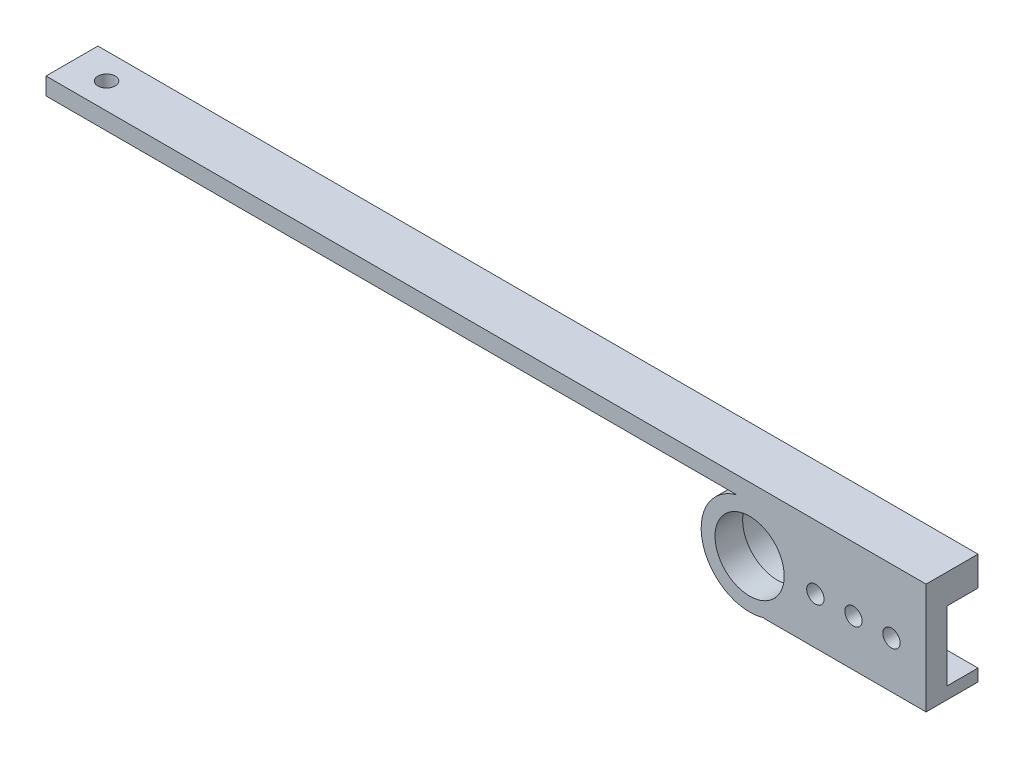
SolidWorks part; units mm, degrees
ref_plane "前视基准面" through (0, 0, 0) normal (0, 0, 1) x (1, 0, 0)
ref_plane "上视基准面" through (0, 0, 0) normal (0, 1, 0) x (1, 0, 0)
ref_plane "右视基准面" through (0, 0, 0) normal (1, 0, 0) x (0, 0, -1)
sketch "草图1" plane through (0, 0, 0) normal (0, 0, 1) x (1, 0, 0)
  line L1 (20, -10) -> (-20, -10)
  line L2 (20, -10) -> (20, 10)
  line L3 (20, 10) -> (-20, 10)
  line L4 (-20, -10) -> (-20, 10)
  line L5 (20, -10) -> (-20, 10) construction
  line L6 (20, 10) -> (-20, -10) construction
  point P0 (0, 0)
  dimension "D1" = 40
  dimension "D2" = 20
extrude "凸台-拉伸1" add sketch "草图1" along normal blind 6
sketch "草图2" plane through (0, 0, 6) normal (0, 0, 1) x (1, 0, 0)
  line L0 (20, -10) -> (20, 10) construction
  circle A0 centre (10, 0) radius 2.5
  circle A1 centre (-1, 0) radius 2.5
  circle A2 centre (-12, 0) radius 2.5
  dimension "D1" = 10
  dimension "D2" = 5
  dimension "D3" = 3
extrude "切除-拉伸1" cut sketch "草图2" against normal through all
sketch "草图3" plane through (0, 0, 6) normal (0, 0, 1) x (1, 0, 0)
  line L0 (20, 13.5) -> (20, 10)
  line L1 (20, -13.5) -> (-26.894, -13.5)
  line L3 (20, 13.5) -> (-26.894, 13.5)
  line L4 (-20, 10) -> (-20, -10)
  line L5 (-20, -10) -> (20, -10)
  line L6 (20, -10) -> (20, 10)
  line L7 (20, 10) -> (-20, 10)
  line L8 (-20, 10) -> (-20, -10)
  line L9 (-20, -10) -> (20, -10)
  line L10 (20, -10) -> (20, 10)
  line L11 (20, 10) -> (-20, 10)
  line L12 (-26.894, -13.5) -> (-26.894, 13.5)
  line L13 (20, -10.0394) -> (-26.894, 13.5) construction
  line L14 (20, 10.0394) -> (-26.894, -13.5) construction
  line L15 (20, -10) -> (20, -13.5)
  circle A0 centre (-31, 0) radius 11
  circle A1 centre (-31, 0) radius 14
  point P2 (0, 0)
  line M10 (-20, 10) -> (-20, -10)
  line M11 (-20, -10) -> (20, -10)
  line M13 (20, 10) -> (-20, 10)
  dimension "D3" = 22
  dimension "D4" = 28
  dimension "D2" = 3.5
  dimension "D1" = 0
extrude "凸台-拉伸2" add sketch "草图3" against normal blind 15 contours L3 A1 L1 L12 A0 | A1 L1 L15 M11 M10 | L1 A1 L8 A0 L12 | L8 A1 L3 L12 A0 | L8 A1 | A1 L0 L3 M10 M13 region at (-1.9449, 11.7771, 6) region at (-1.9449, -11.7771, 6) region at (-23.0173, 9.0328, 6) region at (-27.2274, 11.7946, 6) region at (-18.7882, 0, 6) region at (-23.0173, -9.0328, 6)
sketch "草图5" plane through (0, 0, 6) normal (0, 0, 1) x (1, 0, 0)
  circle A0 centre (-31, 0) radius 10
  circle A1 centre (-31, 0) radius 11 construction
  circle A2 centre (-31, 0) radius 11
  dimension "D1" = 20
extrude "凸台-拉伸3" add sketch "草图5" against normal blind 8
sketch "草图6" plane through (0, 0, 6) normal (0, 0, 1) x (1, 0, 0)
  circle A0 centre (-31, 0) radius 8.5
  circle A1 centre (-31, 0) radius 10 construction
  circle A2 centre (-31, 0) radius 10
  dimension "D1" = 17
sketch "草图7" plane through (0, 13.5, 0) normal (0, 1, 0) x (1, 0, 0)
  circle A0 centre (-17.1666, 1.953) radius 2.6594
sketch "草图8" plane through (20, 0, 0) normal (1, 0, 0) x (0, 0, -1)
  line L1 (-6, 13.5) -> (9, 13.5)
  line L2 (-6, 13.5) -> (-6, 18.5)
  line L3 (-6, 18.5) -> (9, 18.5)
  line L4 (9, 13.5) -> (9, 18.5)
  dimension "D1" = 5
extrude "凸台-拉伸4" add sketch "草图8" against normal blind 500
sketch "草图9" plane through (0, 0, -9) normal (0, 0, -1) x (-1, 0, 0)
  line L1 (24.4567, 15.8334) -> (28.494, 15.8334)
  line L2 (24.4567, 15.8334) -> (24.4567, 12.469)
  line L3 (24.4567, 12.469) -> (28.494, 12.469)
  line L4 (28.494, 15.8334) -> (28.494, 12.469)
extrude "凸台-拉伸5" add sketch "草图9" against normal through all
sketch "草图10" plane through (0, 18.5, 0) normal (0, 1, 0) x (1, 0, 0)
  line L0 (-234.3163, -11.8999) -> (-234.3163, 9)
  line L1 (-234.3163, -11.8999) -> (-86.5711, -11.8999) construction
  line L2 (-234.3163, 238.5858) -> (-234.3163, -131.4142) construction
  line L3 (-480, 9) -> (20, 9) construction
sketch "草图11" plane through (0, 18.5, 0) normal (0, 1, 0) x (1, 0, 0)
  line L1 (-234.3163, -11.8999) -> (-495.6366, -11.8999)
  line L2 (-234.3163, -11.8999) -> (-234.3163, 25.3653)
  line L3 (-234.3163, 25.3653) -> (-495.6366, 25.3653)
  line L4 (-495.6366, -11.8999) -> (-495.6366, 25.3653)
extrude "切除-拉伸2" cut sketch "草图11" against normal through all
sketch "草图12" plane through (0, 18.5, 0) normal (0, 1, 0) x (1, 0, 0)
  line L0 (-234.3163, 9) -> (-234.3163, -6) construction
  line L1 (-234.3163, 1.5) -> (-224.3163, 1.5) construction
  circle A0 centre (-224.3163, 1.5) radius 2.5
  dimension "D1" = 5
  dimension "D2" = 10
extrude "切除-拉伸3" cut sketch "草图12" against normal through all
